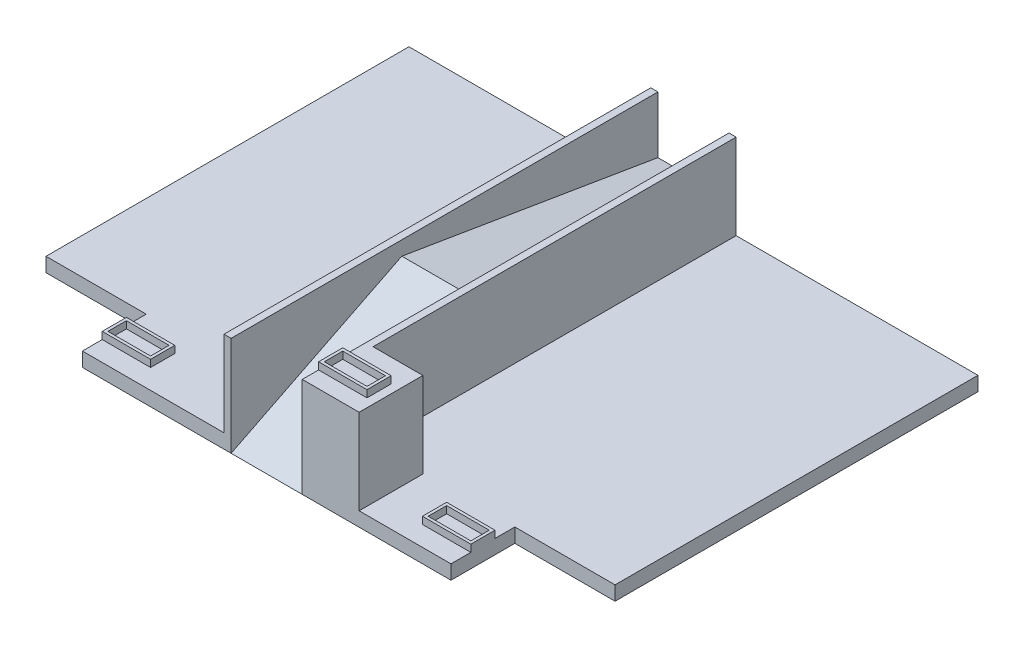
SolidWorks part; units mm, degrees
ref_plane "Front Plane" through (0, 0, 0) normal (0, 0, 1) x (1, 0, 0)
ref_plane "Top Plane" through (0, 0, 0) normal (0, 1, 0) x (1, 0, 0)
ref_plane "Right Plane" through (0, 0, 0) normal (1, 0, 0) x (0, 0, -1)
sketch "Sketch1" plane through (0, 0, 0) normal (0, 1, 0) x (1, 0, 0)
  line L1 (-100.4558, 255.2091) -> (299.5442, 255.2091)
  line L2 (-100.4558, 255.2091) -> (-100.4558, 0.0925)
  line L3 (-30, -44.7909) -> (229.0884, -44.7909)
  line L5 (-100.4558, 0.0925) -> (-30, 0.0925)
  line L8 (-30, 0.0925) -> (-30, -44.7909)
  line L23 (99.5442, 255.2091) -> (99.5442, -44.7909) construction
  line L32 (299.5442, 0.0925) -> (229.0884, 0.0925)
  line L33 (299.5442, 255.2091) -> (299.5442, 0.0925)
  line L34 (229.0884, 0.0925) -> (229.0884, -44.7909)
  point P1 (0, 0)
  point P32 (199.0884, -22.3492)
  dimension "D3" = 200
  dimension "D4" = 300
  dimension "D2" = 44.8834
  dimension "D11" = 70.4558
  dimension "D12" = 129.5442
extrude "Boss-Extrude3" add sketch "Sketch1" along normal blind 10
sketch "Sketch2" plane through (0, 10, 0) normal (0, 1, 0) x (1, 0, 0)
  line L0 (-30, 0.0925) -> (-30, -44.7909) construction
  line L1 (-30, -13.8492) -> (4, -13.8492)
  line L3 (-30, -13.8492) -> (-30, -30.8492)
  line L4 (-30, -30.8492) -> (4, -30.8492)
  line L5 (4, -13.8492) -> (4, -30.8492)
  line L6 (-13, -13.8492) -> (-13, -30.8492) construction
  line L7 (-28, -15.8492) -> (2, -15.8492)
  line L8 (-28, -15.8492) -> (-28, -28.8492)
  line L9 (-28, -28.8492) -> (2, -28.8492)
  line L10 (2, -15.8492) -> (2, -28.8492)
  line L11 (4, -22.3492) -> (-30, -22.3492) construction
  line L12 (-30, -44.7909) -> (229.0884, -44.7909) construction
  line L13 (99.5442, 255.2091) -> (99.5442, -44.7909) construction
  line L14 (299.5442, 255.2091) -> (-100.4558, 255.2091) construction
  line L15 (195.0884, -22.3492) -> (229.0884, -22.3492) construction
  line L16 (212.0884, -13.8492) -> (212.0884, -30.8492) construction
  line L17 (197.0884, -15.8492) -> (197.0884, -28.8492)
  line L18 (227.0884, -28.8492) -> (197.0884, -28.8492)
  line L19 (227.0884, -15.8492) -> (227.0884, -28.8492)
  line L20 (227.0884, -15.8492) -> (197.0884, -15.8492)
  line L21 (195.0884, -13.8492) -> (195.0884, -30.8492)
  line L22 (229.0884, -30.8492) -> (195.0884, -30.8492)
  line L23 (229.0884, -13.8492) -> (229.0884, -30.8492)
  line L24 (229.0884, -13.8492) -> (195.0884, -13.8492)
  dimension "D1" = 2
  dimension "D2" = 2
  dimension "D3" = 2
  dimension "D4" = 2
  dimension "D5" = 30
  dimension "D6" = 13
  dimension "D7" = 22.4417
extrude "Boss-Extrude4" add sketch "Sketch2" along normal blind 5
sketch "Sketch3" plane through (0, 10, 0) normal (0, 1, 0) x (1, 0, 0)
  line L0 (99.5442, 255.2091) -> (99.5442, -44.7909) construction
  line L1 (299.5442, 255.2091) -> (-100.4558, 255.2091) construction
  line L2 (-30, -44.7909) -> (229.0884, -44.7909) construction
  line L3 (74.5442, -44.7909) -> (74.5442, 75.2091)
  line L4 (74.5442, 75.2091) -> (124.5442, 75.2091)
  line L5 (124.5442, 75.2091) -> (124.5442, -44.7909)
  line L22 (195.0884, -30.8492) -> (195.0884, -13.8492)
  line L23 (195.0884, -13.8492) -> (229.0884, -13.8492)
  line L24 (229.0884, -13.8492) -> (229.0884, 0.0925)
  line L25 (229.0884, 0.0925) -> (299.5442, 0.0925)
  line L26 (299.5442, 0.0925) -> (299.5442, 255.2091)
  line L27 (299.5442, 255.2091) -> (-100.4558, 255.2091)
  line L28 (-100.4558, 255.2091) -> (-100.4558, 0.0925)
  line L29 (-100.4558, 0.0925) -> (-30, 0.0925)
  line L30 (-30, 0.0925) -> (-30, -13.8492)
  line L31 (-30, -13.8492) -> (4, -13.8492)
  line L32 (4, -13.8492) -> (4, -30.8492)
  line L33 (4, -30.8492) -> (-30, -30.8492)
  line L34 (-30, -30.8492) -> (-30, -44.7909)
  line L35 (-30, -44.7909) -> (229.0884, -44.7909)
  line L36 (229.0884, -44.7909) -> (229.0884, -30.8492)
  line L37 (229.0884, -30.8492) -> (195.0884, -30.8492)
  line L51 (74.5442, -44.7909) -> (124.5442, -44.7909)
  dimension "D1" = 50
  dimension "D2" = 25
  dimension "D3" = 120
extrude "Boss-Extrude5" add sketch "Sketch3" along normal blind 50
sketch "Sketch4" plane through (124.5442, 0, 0) normal (1, 0, 0) x (0, 0, -1)
  line L2 (-44.7909, 60) -> (75.2091, 60)
  line L3 (75.2091, 60) -> (-44.7909, 0)
  line L4 (-44.7909, 60) -> (-44.7909, 0)
extrude "Cut-Extrude2" cut sketch "Sketch4" against normal up to vertex (50 mm away) up to point (74.5442, 60, 44.7909)
sketch "Sketch5" plane through (0, 10, 0) normal (0, 1, 0) x (1, 0, 0)
  line L0 (74.5442, 75.2091) -> (74.5442, 255.2091)
  line L1 (299.5442, 255.2091) -> (-100.4558, 255.2091) construction
  line L2 (74.5442, 255.2091) -> (124.5442, 255.2091)
  line L3 (124.5442, 255.2091) -> (124.5442, 75.2091)
  line L4 (74.5442, 75.2091) -> (124.5442, 75.2091)
  line L5 (74.5442, 75.2091) -> (74.5442, -24.7909) construction
  point P5 (0, 0)
  point P9 (74.5442, 75.2091)
extrude "Boss-Extrude6" add sketch "Sketch5" along normal blind 50
sketch "Sketch6" plane through (124.5442, 0, 0) normal (1, 0, 0) x (0, 0, -1)
  line L2 (75.2091, 60) -> (255.2091, 60)
  line L3 (255.2091, 60) -> (255.2091, 30)
  line L4 (255.2091, 60) -> (255.2091, 10) construction
  line L5 (255.2091, 30) -> (75.2091, 60)
  point P1 (0, 0)
  point P3 (75.2091, 60)
  dimension "D1" = 30
extrude "Cut-Extrude3" cut sketch "Sketch6" against normal through all contours L2 L3 L5
sketch "Sketch7" plane through (0, 0, 0) normal (0, 1, 0) x (1, 0, 0)
  line L0 (69.5442, 255.2091) -> (69.5442, -44.7909)
  line L1 (74.5442, 255.2091) -> (-100.4558, 255.2091) construction
  line L2 (-30, -44.7909) -> (74.5442, -44.7909) construction
  line L3 (69.5442, -44.7909) -> (74.5442, -44.7909)
  line L4 (74.5442, -44.7909) -> (74.5442, 255.2091)
  line L5 (74.5442, 255.2091) -> (74.5442, -24.7909) construction
  line L6 (74.5442, 255.2091) -> (124.5442, 255.2091) construction
  line L7 (74.5442, 255.2091) -> (69.5442, 255.2091)
  line L8 (124.5442, 255.2091) -> (129.5442, 255.2091)
  line L9 (299.5442, 255.2091) -> (124.5442, 255.2091) construction
  line L10 (129.5442, 255.2091) -> (129.5442, -44.7909)
  line L11 (124.5442, -44.7909) -> (229.0884, -44.7909) construction
  line L12 (129.5442, -44.7909) -> (124.5442, -44.7909)
  line L13 (124.5442, -44.7909) -> (124.5442, 255.2091)
  line L14 (129.5442, -44.7909) -> (164.5442, -44.7909)
  line L15 (124.5442, -44.7909) -> (229.0884, -44.7909) construction
  line L16 (164.5442, -44.7909) -> (164.5442, 0)
  line L17 (164.5442, 0) -> (129.5442, 0)
  dimension "D1" = 5
  dimension "D2" = 5
  dimension "D3" = 35
extrude "Boss-Extrude7" add sketch "Sketch7" along normal blind 70 contours L16 L17 L10 L14 | L7 L0 L3 L4 | L13 L8 L10 L12 region at (147.0442, 0, 22.3954)
sketch "Sketch9" plane through (0, 70, 0) normal (0, 1, 0) x (1, 0, 0)
  line L0 (124.5442, -44.7909) -> (124.5442, 75.2091) construction
  line L1 (124.5442, -16.2909) -> (158.5442, -16.2909)
  line L2 (124.5442, -16.2909) -> (124.5442, -33.2909)
  line L3 (124.5442, -33.2909) -> (158.5442, -33.2909)
  line L4 (158.5442, -16.2909) -> (158.5442, -33.2909)
  line L5 (158.5442, -24.7909) -> (124.5442, -24.7909) construction
  line L6 (126.5442, -18.2909) -> (156.5442, -18.2909)
  line L7 (126.5442, -18.2909) -> (126.5442, -31.2909)
  line L8 (126.5442, -31.2909) -> (156.5442, -31.2909)
  line L9 (156.5442, -18.2909) -> (156.5442, -31.2909)
  line L10 (141.5442, -16.2909) -> (141.5442, -35.4954) construction
  line L11 (164.5442, -44.7909) -> (124.5442, -44.7909) construction
  dimension "D1" = 2
  dimension "D2" = 2
  dimension "D3" = 2
  dimension "D4" = 2
  dimension "D5" = 30
  dimension "D6" = 13
  dimension "D7" = 20
extrude "Boss-Extrude8" add sketch "Sketch9" along normal blind 5 contours L2 L1 L4 L3 | L7 L6 L9 L8
equation "\"draggingScrewDiameter\" = 2"
equation "\"chassisWidth\"= 400"
equation "\"D3@Sketch1\"=0.5 * \"chassisWidth\""
equation "\"chassisLength\"=300"
equation "\"D4@Sketch1\"=\"chassisLength\""
equation "\"wheelDepth\"=44.8834"
equation "\"D2@Sketch1\"=\"wheelDepth\""
equation "\"wheelWidth\"=70.4558"
equation "\"D11@Sketch1\"=\"wheelWidth\""
equation "\"D12@Sketch1\"=(0.5 * \"chassisWidth\") - \"wheelWidth\""
equation "\"baseThickness\"=10"
equation "\"D1@Boss-Extrude3\"=\"baseThickness\""
equation "\"D7@Sketch2\"=\"wheelDepth\" * 0.5"
equation "\"rampLength\"=120"
equation "\"D3@Sketch3\"=\"rampLength\""
equation "\"rampHeight\"=50"
equation "\"D1@Boss-Extrude5\"=\"rampHeight\""
equation "\"D1@Boss-Extrude6\"=\"rampHeight\""
equation "\"dumpHeight\"=30"
equation "\"D1@Sketch6\"=\"dumpHeight\""
